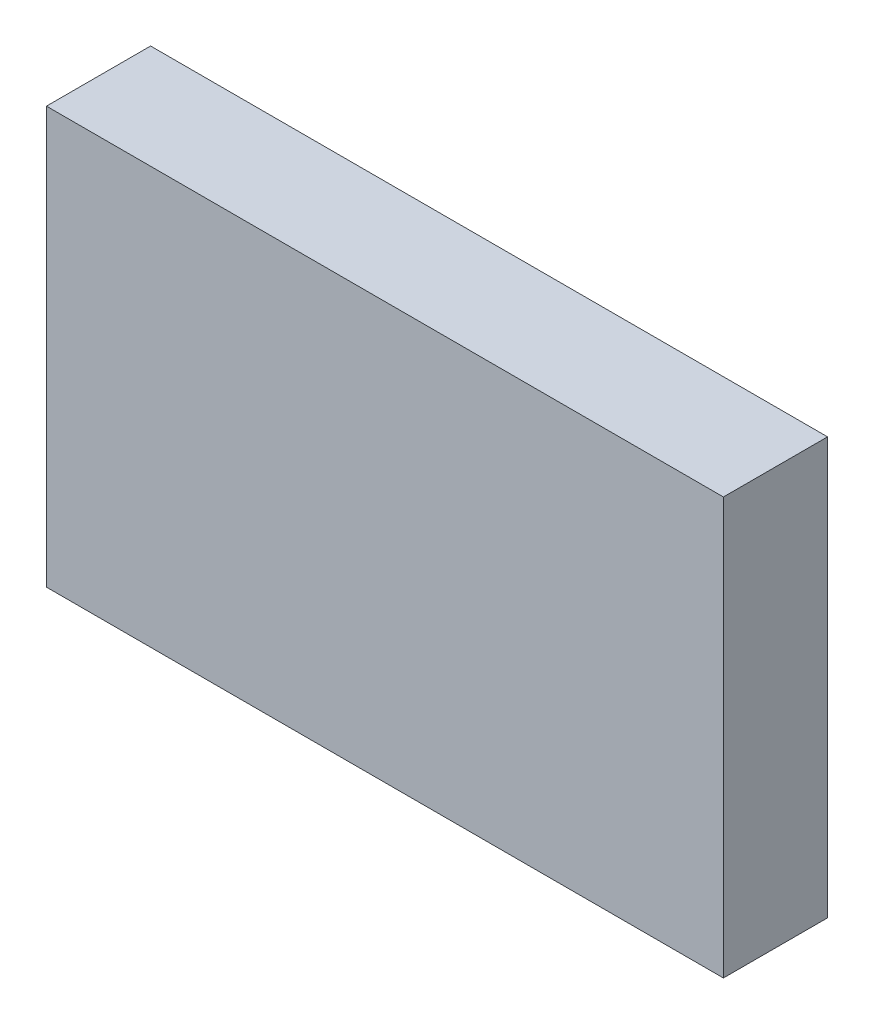
SolidWorks part; units mm, degrees
ref_plane "Front Plane" through (0, 0, 0) normal (0, 0, 1) x (1, 0, 0)
ref_plane "Top Plane" through (0, 0, 0) normal (0, 1, 0) x (1, 0, 0)
ref_plane "Right Plane" through (0, 0, 0) normal (1, 0, 0) x (0, 0, -1)
sketch "Sketch2" plane through (0, 0, 0) normal (0, 1, 0) x (1, 0, 0)
  line L1 (-325, 50) -> (325, 50)
  line L2 (-325, 50) -> (-325, -50)
  line L3 (-325, -50) -> (325, -50)
  line L4 (325, 50) -> (325, -50)
  line L5 (-325, 50) -> (325, -50) construction
  line L6 (-325, -50) -> (325, 50) construction
  point P0 (0, 0)
  dimension "D1" = 650
  dimension "D2" = 100
extrude "Boss-Extrude1" add sketch "Sketch2" along normal blind 200 and the other way blind 200 contours L1 L4 L3 L2
ref_plane "Plane1" through (272, 0, 0) normal (1, 0, 0) x (0, 0, -1)
ref_plane "Plane2" through (-272, 0, 0) normal (1, 0, 0) x (0, 0, -1)
ref_plane "Plane3" through (100, 0, 0) normal (1, 0, 0) x (0, 0, -1)
ref_plane "Plane4" through (-100, 0, 0) normal (1, 0, 0) x (0, 0, -1)
ref_axis "Axis1" through (272, 275, 0) along (0, -1, 0)
ref_axis "Axis2" through (-272, 275, 0) along (0, -1, 0)
ref_axis "Axis3" through (100, 272.0533, 0) along (0, -1, 0)
ref_axis "Axis4" through (-100, 277.5009, 0) along (0, -1, 0)
